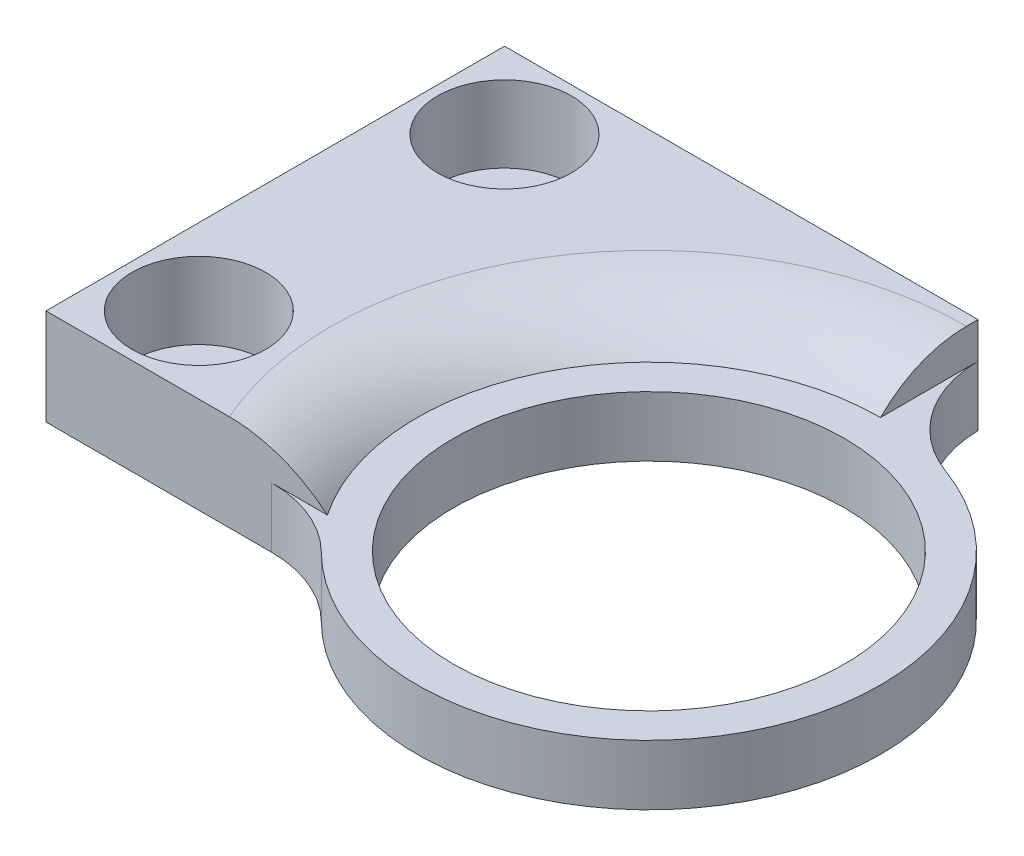
SolidWorks part; units mm, degrees
ref_plane "Front Plane" through (0, 0, 0) normal (0, 0, 1) x (1, 0, 0)
ref_plane "Top Plane" through (0, 0, 0) normal (0, 1, 0) x (1, 0, 0)
ref_plane "Right Plane" through (0, 0, 0) normal (1, 0, 0) x (0, 0, -1)
sketch "Sketch1" plane through (0, 0, 0) normal (0, 1, 0) x (1, 0, 0)
  circle A0 centre (0, 0) radius 16.25
  circle A1 centre (0, 0) radius 19.25
  dimension "D1" = 32.5
  dimension "D2" = 3
extrude "Boss-Extrude1" add sketch "Sketch1" along normal blind 5
sketch "Sketch2" plane through (0, 0, 0) normal (0, 1, 0) x (1, 0, 0)
  line L5 (-39.35, 27.35) -> (0, 27.35)
  line L6 (-39.35, 27.35) -> (-39.35, -10.75)
  line L7 (-39.35, -10.75) -> (0, -10.75)
  line L8 (0, 27.35) -> (0, -10.75)
  circle A3 centre (-33, 21) radius 3.175 construction
  circle A4 centre (-33, -4.4) radius 3.175 construction
  circle A5 centre (0, 0) radius 19.25
  circle A6 centre (0, 0) radius 19.25
  dimension "D1" = 6.35
  dimension "D2" = 6.35
  dimension "D3" = 6.35
  dimension "D5" = 0
extrude "Boss-Extrude2" add sketch "Sketch2" along normal blind 8 contours A6 L8 L5 L6 L7 region at (-25.0201, 0, -10.9485)
hole_wizard "CBORE for 1/4 Socket Head Cap Screw1" positions "Sketch5" profile "Sketch6" counterbore size "1/4" standard "ANSI Inch" end condition through all
sketch "Sketch5" plane through (0, 8, 0) normal (0, 1, 0) x (1, 0, 0)
  point P0 (-33, 21)
  point P3 (-33, -4.4)
sketch "Sketch6" plane through (-33, 8, -21) normal (1, 0, 0) x (0, 0, 1)
  line L0 (0, 0) -> (0, 8)
  line L1 (0, 8) -> (3.3782, 8)
  line L3 (3.3782, 8) -> (3.3782, 6.35)
  line L4 (3.3782, 6.35) -> (5.5562, 6.35)
  line L5 (5.5562, 6.35) -> (5.5562, 0)
  line L7 (5.5562, 0) -> (0, 0)
  line L11 (0, -6.35) -> (0, 107.95) construction
  dimension "Thru Hole Dia." = 6.7564
  dimension "Thru Hole Depth" = 8
  dimension "C'Bore Dia." = 11.1125
  dimension "C'Bore Depth" = 6.35
fillet "Fillet1" radius 10 3 edges at (-16.9926, 8, -9.045) (-15.9687, 2.5, 10.75) (0, 2.5, -19.25)
